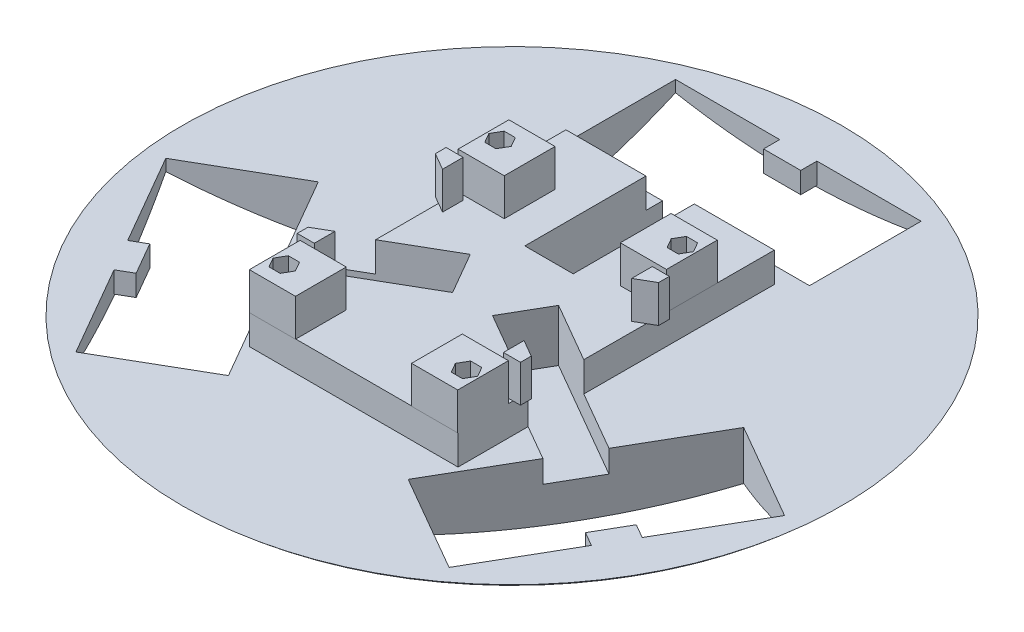
SolidWorks part; units mm, degrees
ref_plane "Front Plane" through (0, 0, 0) normal (0, 0, 1) x (1, 0, 0)
ref_plane "Top Plane" through (0, 0, 0) normal (0, 1, 0) x (1, 0, 0)
ref_plane "Right Plane" through (0, 0, 0) normal (1, 0, 0) x (0, 0, -1)
sketch "Sketch2" plane through (0, 0, 0) normal (0, 1, 0) x (1, 0, 0)
  line L0 (0, -68.0098) -> (0, 65.7503) construction
  line L1 (-33, 76.9495) -> (33, 76.9495)
  line L2 (-33, 76.9495) -> (-33, 46.9495)
  line L3 (-33, 46.9495) -> (33, 46.9495)
  line L4 (33, 76.9495) -> (33, 46.9495)
  line L5 (-33, 76.9495) -> (33, 46.9495) construction
  line L6 (-33, 46.9495) -> (33, 76.9495) construction
  line L7 (-70.2148, 0) -> (95.7201, 0) construction
  line L8 (0, 0) -> (-72.5813, -41.9048) construction
  line L9 (0, 0) -> (72.5813, -41.9048) construction
  line L10 (83.1402, -9.8959) -> (50.1402, -67.0536)
  line L11 (57.1594, 5.1041) -> (24.1594, -52.0536)
  line L12 (83.1402, -9.8959) -> (57.1594, 5.1041)
  line L13 (50.1402, -67.0536) -> (24.1594, -52.0536)
  line L14 (-50.1402, -67.0536) -> (-83.1402, -9.8959)
  line L15 (-24.1594, -52.0536) -> (-57.1594, 5.1041)
  line L16 (-50.1402, -67.0536) -> (-24.1594, -52.0536)
  line L17 (-83.1402, -9.8959) -> (-57.1594, 5.1041)
  line L18 (-6.5, -8.0505) -> (6.5, 46.9495) construction
  line L19 (-6.5, 46.9495) -> (6.5, 46.9495)
  line L20 (-6.5, 46.9495) -> (-6.5, -8.0505)
  line L21 (-6.5, -8.0505) -> (6.5, -8.0505)
  line L22 (6.5, 46.9495) -> (6.5, -8.0505)
  line L23 (-6.5, 46.9495) -> (6.5, -8.0505) construction
  line L24 (31.4023, -15.1408) -> (6.5, -0.7634)
  line L25 (-6.1216, -8.0505) -> (0, 2.5524)
  line L26 (24.9023, -26.3991) -> (0, -12.0218)
  line L27 (-25.0514, -26.4852) -> (0, -12.0218)
  line L28 (0, 2.5524) -> (6.1216, -8.0505)
  line L29 (-33.4324, -16.3129) -> (-6.5, -0.7634)
  circle A2 centre (0, 0) radius 16 construction
  point P3 (0, 19.4495)
  point P4 (0, 46.9495)
  point P6 (0, 61.9495)
  point P13 (0, 0)
  point P33 (0, 0)
  point P41 (0, -4.5162)
  dimension "D1" = 55
  dimension "D2" = 13
  dimension "D3" = 32
  dimension "D5" = 66
  dimension "D6" = 120
  dimension "D7" = 30
  dimension "D8" = 3
  dimension "D4" = 3
sketch "Sketch3" plane through (0, 0, 0) normal (1, 0, 0) x (0, 0, -1)
  line L0 (0, 83.7838) -> (0, -101.0811) construction
  line L1 (-115.9459, 0) -> (127.2973, 0) construction
  line L5 (0, 20) -> (0, 0)
  line L6 (88.569, 20) -> (0, 20)
  arc A3 (84.754, 17.3868) -> (0, 0) centre (7.3808, 179.2865) cw
  arc A4 (84.754, 17.3868) -> (88.569, 20) centre (78.286, 30.9207) ccw
  point P13 (90, 5.0684)
  dimension "D5" = 179.4384
  dimension "D1" = 15
  dimension "D2" = 20
  dimension "D3" = 20
  dimension "D4" = 90
revolve "Revolve1" add sketch "Sketch3" angle 360 about L5
extrude "Cut-Extrude1" cut sketch "Sketch2" along normal blind 40 contours L3 L4 L1 L2 | L15 L17 L14 L16 | L11 L13 L10 L12
sketch "Sketch4" plane through (0, 20, 0) normal (0, 1, 0) x (1, 0, 0)
  line L1 (-6.5, 46.9495) -> (6.5, 46.9495)
  line L2 (-6.5, 46.9495) -> (-6.5, 9.9495)
  line L3 (-6.5, 9.9495) -> (6.5, 9.9495)
  line L4 (6.5, 46.9495) -> (6.5, 9.9495)
  line L5 (-6.5, 46.9495) -> (6.5, 9.9495) construction
  line L6 (-6.5, 9.9495) -> (6.5, 46.9495) construction
  line L7 (43.9094, -17.8456) -> (37.4094, -29.1039)
  line L8 (-57.1594, 5.1041) -> (-24.1594, -52.0536) construction
  line L9 (-33, 46.9495) -> (33, 46.9495) construction
  line L10 (57.1594, 5.1041) -> (24.1594, -52.0536) construction
  line L26 (43.9094, -17.8456) -> (11.8665, 0.6544)
  line L27 (37.4094, -29.1039) -> (5.3665, -10.6039)
  line L28 (11.8665, 0.6544) -> (5.3665, -10.6039)
  line L29 (-37.4094, -29.1039) -> (-43.9094, -17.8456)
  line L30 (-37.4094, -29.1039) -> (-5.3665, -10.6039)
  line L31 (-43.9094, -17.8456) -> (-11.8665, 0.6544)
  line L32 (-5.3665, -10.6039) -> (-11.8665, 0.6544)
  line L33 (50.1402, -67.0536) -> (40.4434, -61.4551)
  line L34 (50.1402, -67.0536) -> (24.1594, -52.0536) construction
  line L35 (50.1402, -67.0536) -> (83.1402, -9.8959)
  line L36 (83.1402, -9.8959) -> (73.4434, -4.2974)
  line L37 (83.1402, -9.8959) -> (57.1594, 5.1041) construction
  circle A0 centre (0, 0) radius 88.569 construction
  circle A1 centre (0, 0) radius 73.569 construction
  arc A2 (40.4434, -61.4551) -> (73.4434, -4.2974) centre (0, 0) ccw
  circle A3 centre (0, 0) radius 83.7271
  point P0 (0, 28.4495)
  point P5 (0, 46.9495)
  point P22 (0, 0)
  point P23 (0, 4.0327)
  point P32 (-2.3282, 4.0326)
  line M8 (-57.1594, 5.1041) -> (-24.1594, -52.0536)
  line M13 (24.1594, -52.0536) -> (57.1594, 5.1041)
  line M17 (33, 46.9495) -> (-33, 46.9495)
  dimension "D4" = 177.1379
  dimension "D5" = 147.1379
  dimension "D6" = 167.4541
  dimension "D1" = 13
  dimension "D2" = 37
  dimension "D3" = 15
extrude "Cut-Extrude2" cut sketch "Sketch4" against normal blind 6 contours L4 L2 L3 M17 | L30 L32 L31 M8 | L26 L28 L27 M13 region at (0, 20, -28.4495) region at (24.638, 20, 14.2247) region at (-24.638, 20, 14.2247)
sketch "Sketch5" plane through (0, 20, 0) normal (0, 1, 0) x (1, 0, 0)
  line L1 (-28, 42.5) -> (-6.5, 42.5)
  line L2 (-28, 42.5) -> (-28, -8.6603)
  line L3 (-28, -42.5) -> (28, -42.5)
  line L5 (-28, 42.5) -> (28, -42.5) construction
  line L6 (-28, -42.5) -> (28, 42.5) construction
  line L7 (-37.4094, -29.1039) -> (-5.3665, -10.6039) construction
  line L10 (-43.9094, -17.8456) -> (-11.8665, 0.6544) construction
  line L12 (37.4094, -29.1039) -> (5.3665, -10.6039) construction
  line L18 (6.5, 46.9495) -> (6.5, 9.9495) construction
  line L19 (6.5, 46.9495) -> (6.5, 9.9495) construction
  line L20 (-28, -23.6714) -> (-28, -42.5)
  line L21 (28, -23.6714) -> (28, -42.5)
  line L22 (6.5, 42.5) -> (28, 42.5)
  line L23 (0, 13.9495) -> (0, -42.8187) construction
  line L24 (28, 42.5) -> (27.888, -8.5956)
  line L26 (-6.5, 46.9495) -> (-6.5, 9.9495) construction
  line L27 (43.9094, -17.8456) -> (11.8665, 0.6544) construction
  line L28 (27.888, -8.5956) -> (11.8665, 0.6544)
  line L29 (11.8665, 0.6544) -> (5.3665, -10.6039)
  line L30 (-28, -8.6603) -> (-11.8665, 0.6544)
  line L31 (-11.8665, 0.6544) -> (-5.3665, -10.6039)
  line L32 (-6.5, 42.5) -> (-6.5, 9.9495)
  line L33 (-6.5, 9.9495) -> (6.5, 9.9495)
  line L34 (-5.3665, -10.6039) -> (-28, -23.6714)
  line L35 (5.3665, -10.6039) -> (28, -23.6714)
  line L36 (6.5, 9.9495) -> (6.5, 42.5)
  line L40 (0, -51.0669) -> (0, 44.2573) construction
  line L41 (-47.7731, 0) -> (43.2855, 0) construction
  point P0 (0, 0)
  dimension "D1" = 56
  dimension "D2" = 85
extrude "Boss-Extrude1" add sketch "Sketch5" along normal blind 8
sketch "Sketch6" plane through (0, 28, 0) normal (0, 1, 0) x (1, 0, 0)
  line L0 (-15.5977, 13.519) -> (-15.5977, 27.1605)
  line L1 (-15.5977, 27.1605) -> (-28, 27.1605)
  line L2 (-28, 27.1605) -> (-28, 13.519)
  line L3 (-28, 13.519) -> (-15.5977, 13.519)
  line L4 (-28, 42.5) -> (-28, -8.6603) construction
  line L5 (21.4978, 21.2855) -> (22.9989, 23.8855)
  line L6 (0, -54.2519) -> (0, 64.1127) construction
  line L7 (-46.6508, -7.7145) -> (37.9333, -7.7145) construction
  line L8 (28, 13.519) -> (15.5977, 13.519)
  line L9 (15.5977, 13.519) -> (15.5977, 27.1605)
  line L10 (15.5977, 27.1605) -> (28, 27.1605)
  line L11 (28, 27.1605) -> (28, 13.519)
  line L12 (15.5977, -28.948) -> (15.5977, -42.5894)
  line L13 (28, -28.948) -> (15.5977, -28.948)
  line L14 (28, -42.5894) -> (28, -28.948)
  line L15 (15.5977, -42.5894) -> (28, -42.5894)
  line L16 (-28, -42.5894) -> (-28, -28.948)
  line L17 (-28, -28.948) -> (-15.5977, -28.948)
  line L18 (-15.5977, -28.948) -> (-15.5977, -42.5894)
  line L19 (-15.5977, -42.5894) -> (-28, -42.5894)
  line L20 (-21.4978, 21.2855) -> (-22.9989, 23.8855)
  line L21 (-22.9989, 23.8855) -> (-26.0011, 23.8855)
  line L22 (-26.0011, 23.8855) -> (-27.5022, 21.2855)
  line L23 (-27.5022, 21.2855) -> (-26.0011, 18.6855)
  line L24 (-26.0011, 18.6855) -> (-22.9989, 18.6855)
  line L25 (-22.9989, 18.6855) -> (-21.4978, 21.2855)
  line L26 (22.9989, 18.6855) -> (21.4978, 21.2855)
  line L27 (26.0011, 18.6855) -> (22.9989, 18.6855)
  line L28 (27.5022, 21.2855) -> (26.0011, 18.6855)
  line L29 (26.0011, 23.8855) -> (27.5022, 21.2855)
  line L30 (22.9989, 23.8855) -> (26.0011, 23.8855)
  line L31 (-21.4978, -36.7145) -> (-22.9989, -39.3145)
  line L32 (-22.9989, -39.3145) -> (-26.0011, -39.3145)
  line L33 (-26.0011, -39.3145) -> (-27.5022, -36.7145)
  line L34 (-27.5022, -36.7145) -> (-26.0011, -34.1145)
  line L35 (-26.0011, -34.1145) -> (-22.9989, -34.1145)
  line L36 (-22.9989, -34.1145) -> (-21.4978, -36.7145)
  line L37 (26.0011, -39.3145) -> (27.5022, -36.7145)
  line L38 (22.9989, -39.3145) -> (26.0011, -39.3145)
  line L39 (21.4978, -36.7145) -> (22.9989, -39.3145)
  line L40 (22.9989, -34.1145) -> (21.4978, -36.7145)
  line L41 (26.0011, -34.1145) -> (22.9989, -34.1145)
  line L42 (27.5022, -36.7145) -> (26.0011, -34.1145)
  circle A0 centre (-24.5, 21.2855) radius 2.6 construction
  dimension "D3" = 5.2
  dimension "D1" = 29
  dimension "D2" = 24.5
  dimension "D4" = 15.5977
  dimension "D5" = 13.6415
extrude "Boss-Extrude2" add sketch "Sketch6" along normal blind 10
sketch "Sketch7" plane through (-3.25, 0, -5.6292) normal (0.5, 0, 0.866) x (0.866, 0, -0.5)
  line L0 (-46.9495, 14) -> (-46.9495, 33.5813) construction
  line L1 (-24.7351, 23.7906) -> (-46.9495, 23.7906)
  line L3 (-46.9495, 23.7906) -> (-46.9495, 27.9906)
  line L4 (-46.9495, 27.9906) -> (-24.7351, 27.9906)
  line L5 (-24.7351, 27.9906) -> (-24.7351, 23.7906)
  dimension "D1" = 4.2
  dimension "D2" = 0
  dimension "D3" = 22.2144
sketch "Sketch8" plane through (0, 28, 0) normal (0, 1, 0) x (1, 0, 0)
  line L0 (-30, 12.2855) -> (30, -27.7145) construction
  line L5 (30, 12.2855) -> (-30, -27.7145) construction
  line L6 (0, 9.9495) -> (0, -29.5154) construction
  line L7 (-6.5, 9.9495) -> (6.5, 9.9495) construction
  line L9 (-15.5977, -7.7145) -> (30, -7.7145) construction
  line L10 (-37.4094, -29.1039) -> (-28, -23.6714) construction
  line L14 (30, -9.815) -> (30, -24.8261)
  line L17 (-30, -27.7145) -> (30, -27.7145) construction
  line L18 (30, 12.2855) -> (30, -9.815) construction
  line L19 (30, -24.8261) -> (30, -27.7145) construction
  line L20 (-30, 12.2855) -> (-30, -9.815) construction
  line L22 (-30, -24.8261) -> (-30, -27.7145) construction
  line L23 (-30, -24.8261) -> (-25.4134, -22.178)
  line L24 (-25.4134, -22.178) -> (-25.4134, -27.7145)
  line L25 (-25.4134, -27.7145) -> (-30, -27.7145)
  line L26 (-30, -27.7145) -> (-30, -24.8261)
  line L27 (30, -27.7145) -> (30, -24.8261)
  line L28 (25.4134, -27.7145) -> (30, -27.7145)
  line L29 (25.4134, -22.178) -> (25.4134, -27.7145)
  line L30 (-30, 12.2855) -> (30, 12.2855) construction
  line L31 (-30, 12.2855) -> (-30, 9.3971)
  line L32 (30, 12.2855) -> (30, 9.3971)
  line L33 (25.4134, 12.2855) -> (30, 12.2855)
  line L34 (25.4134, 6.749) -> (25.4134, 12.2855)
  line L35 (-25.4134, 12.2855) -> (-30, 12.2855)
  line L36 (-25.4134, 6.749) -> (-25.4134, 12.2855)
  line L38 (-30, 9.3971) -> (-25.4134, 6.749)
  line L39 (30, -24.8261) -> (25.4134, -22.178)
  line L40 (30, 9.3971) -> (25.4134, 6.749)
  point P4 (0, -7.7145)
  line M28 (27.888, -8.5956) -> (27.9365, 13.519)
  line M42 (-28, 13.519) -> (-28, -8.6603)
  dimension "D1" = 60
  dimension "D2" = 40
extrude "Boss-Extrude3" add sketch "Sketch8" along normal blind 10 contours L40 L33 L34 M28 | L40 L32 L33 M28 | L38 L36 L35 M42 | L31 L38 L35 M42 | L23 L24 L25 L26 | L39 L29 L28 L27 region at (-28.9445, 28, -10.5366) region at (-26.6395, 28, -9.8712) region at (28.9055, 28, -10.5236) region at (26.608, 28, -9.8632)
sketch "Sketch9" plane through (0, 0, -76.9495) normal (0, 0, 1) x (1, 0, 0)
  line L0 (-33, 20) -> (33, 20) construction
  line L1 (0, 20) -> (0, 13.883) construction
  line L2 (-33, 20) -> (-33, 16.9) construction
  line L3 (33, 20) -> (33, 16.9) construction
  line L4 (5, 20) -> (-5, 20)
  line L5 (-5, 20) -> (-5, 14.3349)
  line L6 (-5, 14.3349) -> (5, 14.3349)
  line L7 (0, 14.3349) -> (0, 20)
  line L8 (5, 20) -> (5, 14.3349)
  arc A0 (-33, 16.9) -> (33, 16.9) centre (0, 196.9) ccw
  spline S0 degree 3 poles (33, 16.9) (27.5706, 15.8939) (22.1092, 15.1426) (11.1237, 14.1379) (5.5997, 13.8843) (-1.3449, 13.8827) (-2.7358, 13.8981) (-5.5217, 13.961) (-6.9174, 14.0085) (-11.0901, 14.1984) (-13.8591, 14.388) (-22.1277, 15.1442) (-27.5893, 15.8974) (-33, 16.9) knots 0 0 0 0 0.25 0.25 0.5 0.5 0.5625 0.5625 0.625 0.625 0.75 0.75 1 1 1 1 construction
  line M8 (33, 20) -> (-33, 20)
  dimension "183" = 183
  dimension "D1" = 5
extrude "Boss-Extrude4" add sketch "Sketch9" along normal blind 4.35 contours L6 L7 L4 L5 | L8 L7 L6 M8 region at (2.5, 17.1674, -76.9495) region at (-2.5, 17.1674, -76.9495)
pattern_circular "CirPattern1" count 3 over 360 about axis through (0, 20, 0) along (0, 1, 0) of "Boss-Extrude4"
